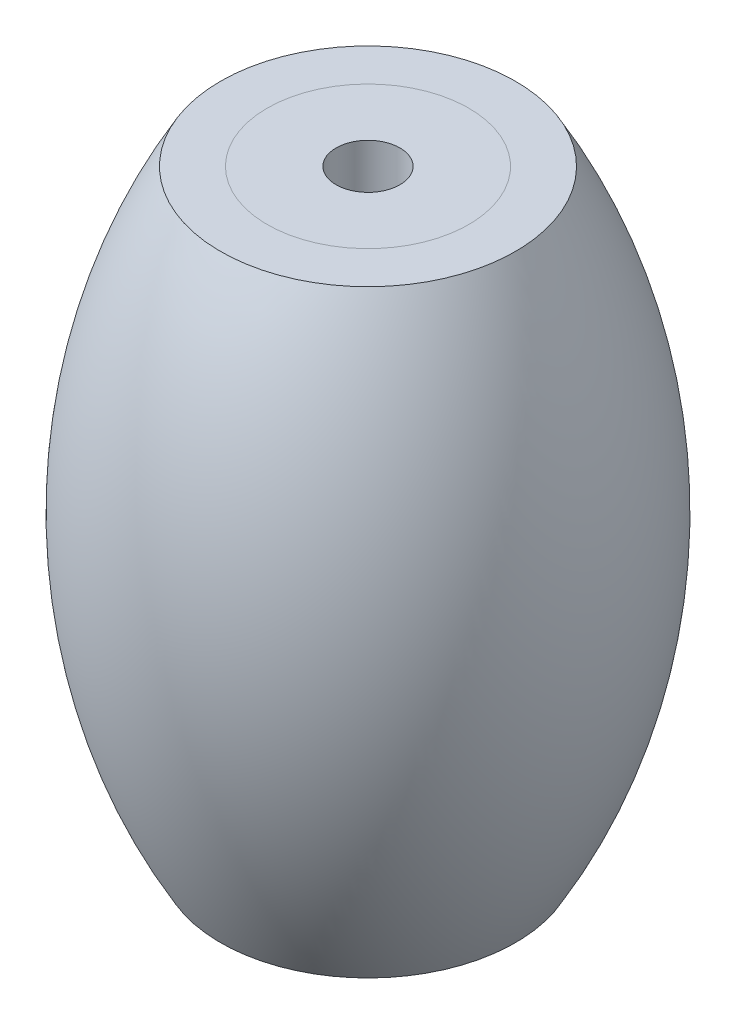
SolidWorks part; units mm, degrees
ref_plane "Front" through (0, 0, 0) normal (0, 0, 1) x (1, 0, 0)
ref_plane "Top" through (0, 0, 0) normal (0, 1, 0) x (1, 0, 0)
ref_plane "Right" through (0, 0, 0) normal (1, 0, 0) x (0, 0, -1)
sketch "Sketch1" plane through (0, 0, 0) normal (0, 0, 1) x (1, 0, 0)
  line L0 (0, 7.5) -> (0, -7.5) construction
  line L1 (0, -7.5) -> (-3.695, -7.5)
  line L2 (0, 7.5) -> (-3.695, 7.5)
  line L3 (9.2954, 0) -> (-3.695, 7.5) construction
  line L4 (9.2954, 0) -> (-3.695, -7.5) construction
  line L5 (-0.8, 7.5) -> (-0.8, -7.5)
  arc A0 (-3.695, 7.5) -> (-3.695, -7.5) centre (9.2954, 0) ccw
  arc A1 (-2.5262, -7.5) -> (-2.5262, 7.5) centre (9.2954, 0) cw
  point P11 (-5.7046, 0)
  dimension "D1" = 15
  dimension "D2" = 3.695
  dimension "D3" = 60
  dimension "D4" = 1.6
  dimension "D5" = 1
  dimension "D6" = 11.4092
revolve "Interior" add sketch "Sketch1" angle 360 about L0 region at (-2.4655, 0, 0)
revolve "Exterior" add sketch "Sketch1<3>" angle 360 about L0 region at (-3.1106, -7.3467, 0)
sketch "Sketch1<3>" plane through (0, 0, 0) normal (0, 0, 1) x (1, 0, 0) same geometry as "Sketch1"
equation "\"wheel_dia\"=30"
equation "\"wheel_rim_room\"=1"
equation "\"miniwheel_top_bottom_room\"=0.7"
equation "\"miniwheel_side_room\"=0.7"
equation "\"miniwheel_axle_dia\"=1.4"
equation "\"miniwheel_axle_holding_room\"=0.5"
equation "\"rim_extra_width\"=0.3"
equation "\"miniwheel_neck_width\"=0.8"
equation "\"middle_thickness\"=8.5"
equation "\"motor_axle_dia\"=3"
equation "\"motor_axle_room\"=0.1"
equation "\"motor_axle_notch_thickness\"=2.5"
equation "\"mate_room\"=0.10"
equation "\"vertical_mate_room\"=0.1"
equation "\"miniwheel_base_dia\"=7.39"
equation "\"D2@Sketch1\"=\"miniwheel_base_dia\"/2"
equation "\"D1@Sketch1\"=\"wheel_dia\"/2"
equation "\"D4@Sketch1\"=\"miniwheel_axle_dia\"+\"miniwheel_axle_room\"*2"
equation "\"miniwheel_axle_room\"=0.1"
equation "\"miniwheel_rubber_thickness\"=1"
equation "\"D5@Sketch1\"=\"miniwheel_rubber_thickness\""
